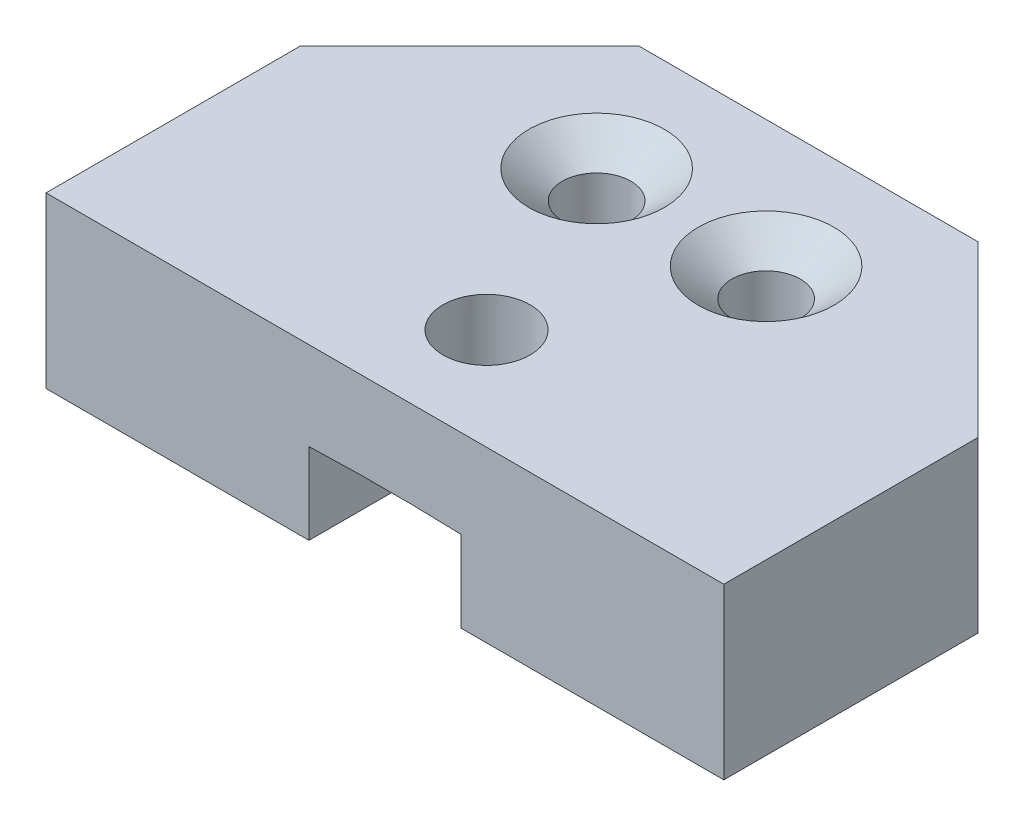
SolidWorks part; units mm, degrees
ref_plane "Front Plane" through (0, 0, 0) normal (0, 0, 1) x (1, 0, 0)
ref_plane "Top Plane" through (0, 0, 0) normal (0, 1, 0) x (1, 0, 0)
ref_plane "Right Plane" through (0, 0, 0) normal (1, 0, 0) x (0, 0, -1)
sketch "Sketch1" plane through (0, 0, 0) normal (0, 1, 0) x (1, 0, 0)
  line L0 (-12.7, 7.9375) -> (12.7, -7.9375) construction
  line L1 (-12.7, 7.9375) -> (12.7, 7.9375)
  line L2 (-12.7, 7.9375) -> (-12.7, -7.9375)
  line L3 (-12.7, -7.9375) -> (12.7, -7.9375)
  line L4 (12.7, 7.9375) -> (12.7, -7.9375)
  point P4 (0, 0)
  dimension "D1" = 15.875
  dimension "D2" = 25.4
extrude "Boss-Extrude1" add sketch "Sketch1" along normal blind 6.35
chamfer "Chamfer1" distance 6.35 angle 45 2 edges at (12.7, 3.175, -7.9375) (-12.7, 3.175, -7.9375)
sketch "Sketch2" plane through (0, 0, 7.9375) normal (0, 0, 1) x (1, 0, 0)
  line L0 (-2.7178, 3.048) -> (-2.7178, 0) construction
  line L1 (-2.7178, 0) -> (2.7178, 0) construction
  line L2 (2.7178, 3.048) -> (2.7178, 0) construction
  line L3 (-12.7, 0) -> (12.7, 0) construction
  line L4 (-2.8448, 3.0434) -> (2.8448, 3.0434) construction
  line L5 (-2.8448, 3.0434) -> (-2.8448, 0)
  line L6 (-2.8448, 0) -> (2.8448, 0)
  line L7 (2.8448, 0) -> (2.8448, 3.0434)
  arc A0 (-2.8448, 3.0434) -> (2.8448, 3.0434) centre (0, -73.1035) cw
  point P7 (0, 0)
  point P9 (2.8834, 2.9284)
  point P12 (0, 0)
  point P15 (-2.2518, 2.9862)
  dimension "D2" = 76.2
  dimension "D1" = 5.4356
  dimension "D3" = 5.6896
  dimension "D4" = 3.048
extrude "Cut-Extrude1" cut sketch "Sketch2" against normal through all
sketch "Sketch3" plane through (0, 6.35, 0) normal (0, 1, 0) x (1, 0, 0)
  circle A0 centre (0, -4.1293) radius 1.6319 construction
  circle A1 centre (0, -4.1293) radius 1.6319
extrude "Cut-Extrude2" cut sketch "Sketch3" against normal through all
hole_wizard "CSK for #10 Flat Head Machine Screw (100)1" positions "Sketch4" profile "Sketch5" countersink size "#10" standard "ANSI Inch" end condition through all
sketch "Sketch4" plane through (0, 6.35, 0) normal (0, 1, 0) x (1, 0, 0)
  circle A0 centre (3.1732, 3.1732) radius 1.8986 construction
  circle A1 centre (3.1732, 3.1732) radius 1.8986 construction
  circle A2 centre (-3.1768, 3.1732) radius 1.8986 construction
  circle A3 centre (-3.1768, 3.1732) radius 1.8986 construction
  point P0 (3.1732, 3.1732)
  point P2 (-3.1768, 3.1732)
  point P5 (0, 0)
  point P12 (0, 0)
  point P13 (0, 0)
sketch "Sketch5" plane through (3.1732, 6.35, -3.1732) normal (1, 0, 0) x (0, 0, 1)
  line L0 (0, 0) -> (0, 6.35)
  line L1 (0, 6.35) -> (1.2827, 6.35)
  line L2 (1.2827, 6.35) -> (1.2827, 1.055)
  line L3 (1.2827, 1.055) -> (2.54, 0)
  line L5 (2.54, 0) -> (0, 0)
  line L6 (-1.2827, 1.055) -> (-2.54, 0) construction
  line L11 (0, -6.35) -> (0, 107.95) construction
  dimension "Thru Hole Dia." = 2.5654
  dimension "Thru Hole Depth" = 6.35
  dimension "Near C'Sink Dia." = 5.08
  dimension "Near C'Sink Angle" = 100
